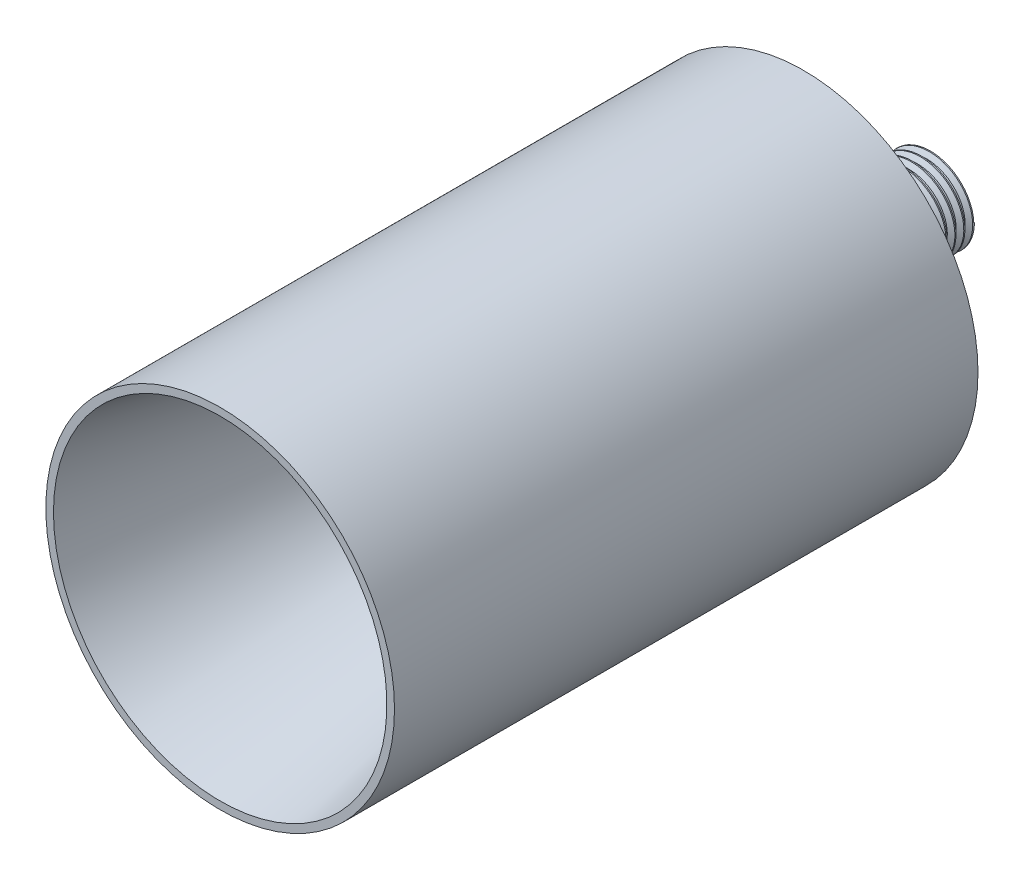
SolidWorks part; units mm, degrees
ref_plane "Front Plane" through (0, 0, 0) normal (0, 0, 1) x (1, 0, 0)
ref_plane "Top Plane" through (0, 0, 0) normal (0, 1, 0) x (1, 0, 0)
ref_plane "Right Plane" through (0, 0, 0) normal (1, 0, 0) x (0, 0, -1)
sketch "Sketch1" plane through (0, 0, 0) normal (0, 0, 1) x (1, 0, 0)
  circle A0 centre (0, 0) radius 6
  circle A1 centre (0, 0) radius 5
  dimension "D1" = 10
  dimension "D2" = 12
extrude "Boss-Extrude1" add sketch "Sketch1" along normal blind 18
sketch "Sketch2" plane through (0, 0, 18) normal (0, 0, 1) x (1, 0, 0)
  circle A0 centre (0, 0) radius 24.5
  circle A1 centre (0, 0) radius 5 construction
  circle A2 centre (0, 0) radius 5
  dimension "D1" = 49
extrude "Boss-Extrude2" add sketch "Sketch2" along normal blind 82
sketch "Sketch4" plane through (0, 0, 18) normal (0, 0, -1) x (-1, 0, 0)
  circle A0 centre (0, 0) radius 6 construction
  circle A1 centre (0, 0) radius 6
extrude "Cut-Extrude1" cut sketch "Sketch4" against normal blind 82 draft 12 draft outward yes
thread "Thread1" pitch 1.25 method cut profile "Thread Profile1" start angle 0, offset 1, length 0, pitch 1.25, diameter 12
ref_plane "Plane1" through (6, 0, -1) normal (0, -1, 0) x (1, 0, 0)
sketch "Thread Profile1" plane through (6, 0, -1) normal (0, -1, 0) x (1, 0, 0)
  line L0 (0, 0) -> (0, 1.25) construction
  line L11 (0, 0) -> (0, 1.0937)
  line L12 (0, 1.0937) -> (-0.6766, 0.7031)
  line L13 (-0.6766, 0.7031) -> (-0.6766, 0.3906)
  line L15 (-0.6766, 0.3906) -> (0, 0)
  line L17 (-0.6766, 0.5469) -> (0, 0.5469) construction
  point P2 (0, 0)
  dimension "Pitch" = 1.25
  dimension "Profile_Angle" = 60
  dimension "Profile_Land" = 0.3125
  dimension "Profile_Height" = 0.6766
